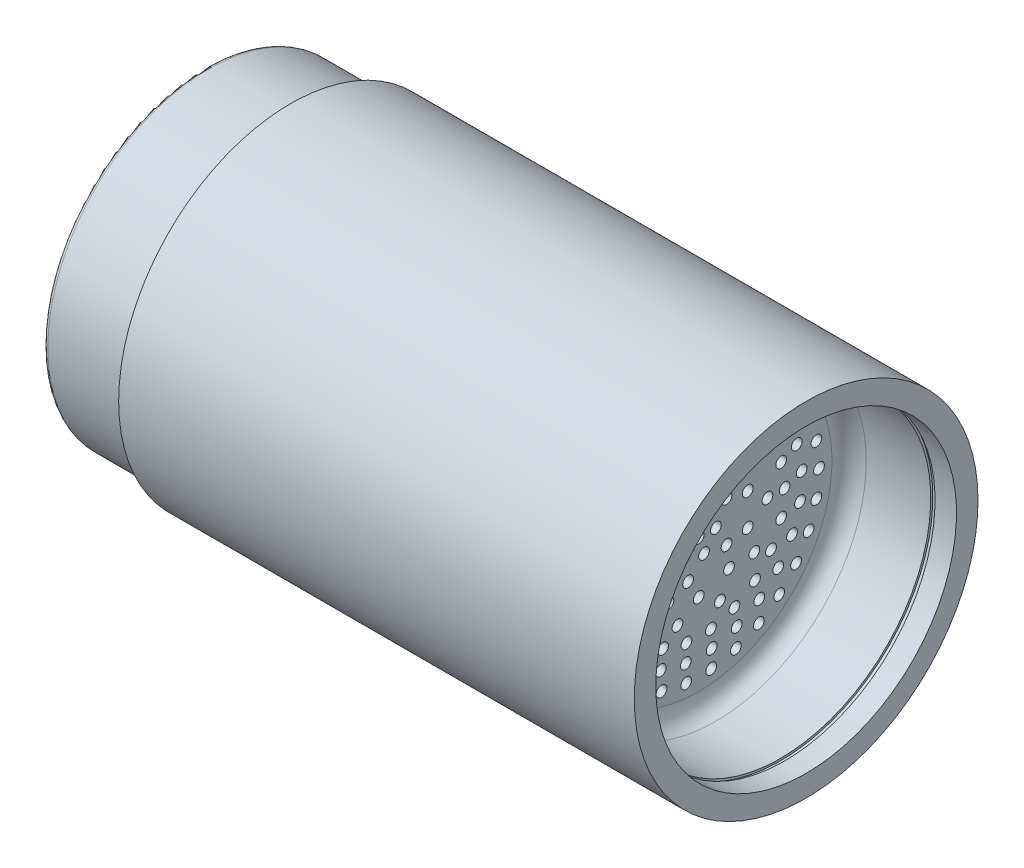
SolidWorks part; units mm, degrees
material "ABS"
ref_plane "Front Plane" through (0, 0, 0) normal (0, 0, 1) x (1, 0, 0)
ref_plane "Top Plane" through (0, 0, 0) normal (0, 1, 0) x (1, 0, 0)
ref_plane "Right Plane" through (0, 0, 0) normal (1, 0, 0) x (0, 0, -1)
sketch "Sketch1" plane through (0, 0, 0) normal (0, 0, 1) x (1, 0, 0)
  line L0 (0, 0) -> (112.0873, 0) construction
  line L1 (112.0873, 0) -> (112.0873, -50.8) construction
  line L2 (112.0873, -50.8) -> (-40.3127, -50.8)
  line L3 (-65.7127, -47.625) -> (-65.7127, -44.45)
  line L4 (-65.7127, -44.45) -> (68.9073, -44.45)
  line L5 (112.0873, -44.45) -> (112.0873, -50.8)
  line L6 (112.0873, -50.8) -> (73.9873, -50.8) construction
  line L7 (73.9873, -39.37) -> (73.9873, 0)
  line L8 (73.9873, 0) -> (80.3373, 0)
  line L9 (80.3373, 0) -> (80.3373, -39.37)
  line L10 (85.4173, -44.45) -> (104.4673, -44.45)
  line L11 (112.0873, -44.45) -> (105.7373, -44.45) construction
  line L12 (105.7373, -44.45) -> (105.7373, -45.085)
  line L13 (105.7373, -45.085) -> (104.4673, -45.085)
  line L14 (104.4673, -45.085) -> (104.4673, -44.45)
  line L15 (105.7373, -44.45) -> (112.0873, -44.45)
  line L16 (-65.7127, -50.8) -> (-40.3127, -50.8) construction
  line L17 (-40.3127, -50.8) -> (-40.3127, -47.625) construction
  line L18 (-40.3127, -47.625) -> (-65.7127, -47.625)
  line L19 (-40.3127, -47.625) -> (-40.3127, -50.8)
  arc A0 (85.4173, -44.45) -> (80.3373, -39.37) centre (85.4173, -39.37) cw
  arc A1 (73.9873, -39.37) -> (68.9073, -44.45) centre (68.9073, -39.37) cw
  point P18 (80.3373, -44.45)
  dimension "D9" = 5.08
  dimension "D1" = 50.8
  dimension "D2" = 177.8
  dimension "D3" = 6.35
  dimension "D4" = 38.1
  dimension "D5" = 6.35
  dimension "D6" = 6.35
  dimension "D7" = 1.27
  dimension "D8" = 0.635
  dimension "D10" = 25.4
revolve "Revolve1" add sketch "Sketch1" angle 360 about L0
sketch "Sketch4" plane through (80.3373, 0, 0) normal (1, 0, 0) x (0, 0, -1)
  circle A0 centre (0, 0) radius 1.5875
  circle A20 centre (5.079, 0) radius 1.5875
  circle A21 centre (1.5695, -4.8304) radius 1.5875
  circle A22 centre (-4.109, -2.9854) radius 1.5875
  circle A23 centre (-4.109, 2.9854) radius 1.5875
  circle A24 centre (0, 15.239) radius 1.5875
  circle A25 centre (8.9573, 12.3286) radius 1.5875
  circle A33 centre (14.4932, 4.7091) radius 1.5875
  circle A34 centre (14.4932, -4.7091) radius 1.5875
  circle A35 centre (8.9573, -12.3286) radius 1.5875
  circle A36 centre (0, -15.239) radius 1.5875
  circle A37 centre (-8.9573, -12.3286) radius 1.5875
  circle A40 centre (20.319, 0) radius 1.5875
  circle A41 centre (16.4384, -11.9432) radius 1.5875
  circle A42 centre (6.2789, -19.3245) radius 1.5875
  circle A43 centre (-6.2789, -19.3245) radius 1.5875
  circle A44 centre (-16.4384, -11.9432) radius 1.5875
  circle A45 centre (-20.319, 0) radius 1.5875
  circle A46 centre (-16.4384, 11.9432) radius 1.5875
  circle A47 centre (-6.2789, 19.3245) radius 1.5875
  circle A48 centre (6.2789, 19.3245) radius 1.5875
  circle A49 centre (16.4384, 11.9432) radius 1.5875
  circle A54 centre (25.399, 0) radius 1.5875
  circle A55 centre (24.3702, -7.1557) radius 1.5875
  circle A56 centre (21.367, -13.7317) radius 1.5875
  circle A57 centre (16.6328, -19.1953) radius 1.5875
  circle A58 centre (10.5511, -23.1038) radius 1.5875
  circle A59 centre (3.6147, -25.1405) radius 1.5875
  circle A60 centre (-3.6147, -25.1405) radius 1.5875
  circle A61 centre (-10.5511, -23.1038) radius 1.5875
  circle A62 centre (-16.6328, -19.1953) radius 1.5875
  circle A63 centre (-21.367, -13.7317) radius 1.5875
  circle A64 centre (-24.3702, -7.1557) radius 1.5875
  circle A65 centre (-25.399, 0) radius 1.5875
  circle A70 centre (0, 30.479) radius 1.5875
  circle A71 centre (7.5798, 29.5215) radius 1.5875
  circle A72 centre (14.6834, 26.709) radius 1.5875
  circle A73 centre (20.8643, 22.2182) radius 1.5875
  circle A74 centre (25.7343, 16.3315) radius 1.5875
  circle A75 centre (28.9873, 9.4185) radius 1.5875
  circle A76 centre (30.4189, 1.9138) radius 1.5875
  circle A77 centre (29.9392, -5.7112) radius 1.5875
  circle A78 centre (27.5782, -12.9773) radius 1.5875
  circle A79 centre (23.4845, -19.4281) radius 1.5875
  circle A80 centre (17.9151, -24.658) radius 1.5875
  circle A81 centre (11.2201, -28.3387) radius 1.5875
  circle A82 centre (3.82, -30.2387) radius 1.5875
  circle A83 centre (-3.82, -30.2387) radius 1.5875
  circle A85 centre (35.559, 0) radius 1.5875
  circle A86 centre (34.782, -7.3931) radius 1.5875
  circle A87 centre (32.4848, -14.4632) radius 1.5875
  circle A88 centre (28.7679, -20.9011) radius 1.5875
  circle A89 centre (23.7936, -26.4255) radius 1.5875
  circle A90 centre (17.7795, -30.795) radius 1.5875
  circle A91 centre (10.9883, -33.8186) radius 1.5875
  circle A92 centre (3.7169, -35.3642) radius 1.5875
  circle A93 centre (-3.7169, -35.3642) radius 1.5875
  circle A94 centre (-10.9883, -33.8186) radius 1.5875
  circle A95 centre (-17.7795, -30.795) radius 1.5875
  circle A96 centre (-23.7936, -26.4255) radius 1.5875
  circle A97 centre (-28.7679, -20.9011) radius 1.5875
  circle A98 centre (-32.4848, -14.4632) radius 1.5875
  circle A99 centre (-34.782, -7.3931) radius 1.5875
  circle A100 centre (-35.559, 0) radius 1.5875
  circle A101 centre (-34.782, 7.3931) radius 1.5875
  circle A102 centre (-32.4848, 14.4632) radius 1.5875
  circle A103 centre (-28.7679, 20.9011) radius 1.5875
  circle A104 centre (-23.7936, 26.4255) radius 1.5875
  circle A105 centre (-17.7795, 30.795) radius 1.5875
  circle A106 centre (-10.9883, 33.8186) radius 1.5875
  circle A107 centre (-11.2201, -28.3387) radius 1.5875
  circle A108 centre (-17.9151, -24.658) radius 1.5875
  circle A109 centre (-23.4845, -19.4281) radius 1.5875
  circle A110 centre (-27.5782, -12.9773) radius 1.5875
  circle A111 centre (-24.3702, 7.1557) radius 1.5875
  circle A112 centre (-21.367, 13.7317) radius 1.5875
  circle A113 centre (-16.6328, 19.1953) radius 1.5875
  circle A115 centre (1.5695, 4.8304) radius 1.5875
  circle A122 centre (-10.159, 0) radius 1.5875
  circle A123 centre (-3.1393, 9.6618) radius 1.5875
  circle A124 centre (8.2188, 5.9713) radius 1.5875
  circle A125 centre (8.2188, -5.9713) radius 1.5875
  circle A126 centre (-3.1393, -9.6618) radius 1.5875
  circle A127 centre (-14.4932, -4.7091) radius 1.5875
  circle A128 centre (-14.4932, 4.7091) radius 1.5875
  circle A129 centre (-8.9573, 12.3286) radius 1.5875
  circle A140 centre (-10.5511, 23.1038) radius 1.5875
  circle A141 centre (-3.6147, 25.1405) radius 1.5875
  circle A142 centre (3.6147, 25.1405) radius 1.5875
  circle A145 centre (-29.9392, -5.7112) radius 1.5875
  circle A146 centre (-30.4189, 1.9138) radius 1.5875
  circle A147 centre (-28.9873, 9.4185) radius 1.5875
  circle A148 centre (-25.7343, 16.3315) radius 1.5875
  circle A149 centre (-20.8643, 22.2182) radius 1.5875
  circle A150 centre (-14.6834, 26.709) radius 1.5875
  circle A151 centre (-7.5798, 29.5215) radius 1.5875
  circle A152 centre (-3.7169, 35.3642) radius 1.5875
  circle A153 centre (3.7169, 35.3642) radius 1.5875
  circle A154 centre (10.9883, 33.8186) radius 1.5875
  circle A155 centre (17.7795, 30.795) radius 1.5875
  circle A156 centre (23.7936, 26.4255) radius 1.5875
  circle A157 centre (28.7679, 20.9011) radius 1.5875
  circle A158 centre (32.4848, 14.4632) radius 1.5875
  circle A159 centre (34.782, 7.3931) radius 1.5875
  circle A160 centre (10.5511, 23.1038) radius 1.5875
  circle A161 centre (16.6328, 19.1953) radius 1.5875
  circle A162 centre (21.367, 13.7317) radius 1.5875
  circle A163 centre (24.3702, 7.1557) radius 1.5875
  point P18 (0, 0)
  point P19 (0, 0)
  point P37 (0, 0)
  point P48 (0, 0)
  point P50 (0, 0)
  point P79 (0, 0)
  point P112 (0, 0)
  point P124 (0, 0)
  point P167 (0, 0)
  point P188 (0, 0)
  dimension "D1" = 5
  dimension "D3" = 10
  dimension "D5" = 5
  dimension "D7" = 10
  dimension "D9" = 22
  dimension "D4" = 25
  dimension "D2" = 30
extrude "Cut-Extrude1" cut sketch "Sketch4" against normal through all both and the other way through all
ref_axis "Axis1" through (112.0873, 0, 0) along (-1, 0, 0)
ref_plane "Plane2" through (10.4873, 0, 0) normal (-1, 0, 0) x (0, 0, 1)
sketch "Sketch5" plane through (10.4873, 0, 0) normal (-1, 0, 0) x (0, 0, 1)
  line L0 (0, 0) -> (-59.3102, 0) construction
  line L1 (0, 0) -> (0, -50.8) construction
  arc A0 (-9.976, 43.3161) -> (9.976, 43.3161) centre (0, 44.45) ccw
  circle A1 centre (0, 0) radius 44.45 construction
  circle A2 centre (0, 0) radius 44.45 construction
  arc A4 (-12.4537, 42.6698) -> (12.4537, 42.6698) centre (0, 44.45) ccw
  arc A6 (12.4537, 42.6698) -> (9.976, 43.3161) centre (0, 0) ccw
  arc A7 (12.5527, 45.2823) -> (-12.5527, 45.2823) centre (0, 0) ccw construction
  arc A8 (-9.976, 43.3161) -> (-12.4537, 42.6698) centre (0, 0) ccw
  arc A9 (-12.5527, 45.2823) -> (12.5527, 45.2823) centre (0, 44.45) ccw construction
  arc A10 (9.976, 43.3161) -> (-9.976, 43.3161) centre (0, 0) ccw construction
  circle A11 centre (0, 0) radius 50.8 construction
  dimension "D1" = 2.54
extrude "Boss-Extrude1" add sketch "Sketch5" against normal blind 50.8
ref_plane "Plane3" through (61.2873, 0, 0) normal (1, 0, 0) x (0, 0, -1)
ref_point "Point1"
sketch "Sketch10" plane through (61.2873, 0, 0) normal (1, 0, 0) x (0, 0, -1)
  line L0 (0, 44.45) -> (-30.0251, 44.45) construction
  arc A0 (-9.976, 43.3161) -> (9.976, 43.3161) centre (0, 44.45) ccw
  arc A1 (-12.4537, 42.6698) -> (12.4537, 42.6698) centre (0, 44.45) ccw
  arc A2 (12.4537, 42.6698) -> (9.976, 43.3161) centre (0, 0) ccw
  arc A3 (-9.976, 43.3161) -> (-12.4537, 42.6698) centre (0, 0) ccw
  circle A4 centre (0, 44.45) radius 12.5803 construction
  circle A5 centre (0, 44.45) radius 10.0403 construction
  point P5 (9.6016, 47.3855)
  point P7 (12.5803, 44.45)
  dimension "D1" = 2.54
revolve "Revolve2" add sketch "Sketch10" angle 90 about L0
sketch "Sketch12" plane through (10.4873, 0, 0) normal (-1, 0, 0) x (0, 0, 1)
  line L0 (0, 0) -> (-52.6904, 0) construction
  line L1 (0, 0) -> (0, -45.085) construction
  line L2 (-7.62, 0) -> (-7.62, -10.45) construction
  line L3 (-45.72, 10.45) -> (-45.72, 11.72)
  line L4 (-7.62, -10.45) -> (-45.72, -10.45)
  line L5 (-7.62, -10.45) -> (-7.62, -11.72)
  line L6 (-7.62, -11.72) -> (-45.72, -11.72)
  line L7 (-45.72, -10.45) -> (-45.72, -11.72)
  line L8 (-7.62, 11.72) -> (-45.72, 11.72)
  line L9 (-7.62, 10.45) -> (-7.62, 11.72)
  line L10 (-7.62, 10.45) -> (-45.72, 10.45)
  line L11 (7.62, 0) -> (7.62, -10.45) construction
  line L12 (7.62, 10.45) -> (45.72, 10.45)
  line L13 (7.62, 10.45) -> (7.62, 11.72)
  line L14 (7.62, 11.72) -> (45.72, 11.72)
  line L15 (45.72, -10.45) -> (45.72, -11.72)
  line L16 (7.62, -11.72) -> (45.72, -11.72)
  line L17 (7.62, -10.45) -> (7.62, -11.72)
  line L18 (7.62, -10.45) -> (45.72, -10.45)
  line L19 (45.72, 10.45) -> (45.72, 11.72)
  circle A1 centre (0, 0) radius 45.085 construction
  dimension "D1" = 10.45
  dimension "D2" = 38.1
  dimension "D3" = 7.62
extrude "Boss-Extrude2" add sketch "Sketch12" against normal up to surface (63.5 mm away) up to face at (73.9873, 0, 26.9865)
ref_plane "Plane5" through (48.5873, 0, 0) normal (-1, 0, 0) x (0, 0, 1)
sketch "Sketch13" plane through (48.5873, 0, 0) normal (-1, 0, 0) x (0, 0, 1)
  line L0 (0, 0) -> (19, 0) construction
  line L1 (19, 0) -> (19, 10.0875)
  line L2 (19, 10.0875) -> (19, 10.45)
  line L3 (27.7805, 10.45) -> (16.9774, 10.45) construction
  line L4 (19, 10.45) -> (20.27, 10.45)
  line L5 (7.62, 10.45) -> (43.2042, 10.45) construction
  line L6 (20.27, 10.45) -> (20.27, -10.45)
  line L7 (16.9774, -10.45) -> (37.9578, -10.45) construction
  line L8 (20.27, -10.45) -> (19, -10.45)
  line L9 (43.2042, -10.45) -> (7.62, -10.45) construction
  line L10 (19, -10.45) -> (19, 0)
  line L11 (0, 0) -> (0, 18.4215) construction
  line L12 (-19, -10.45) -> (-19, 0)
  line L13 (-20.27, -10.45) -> (-19, -10.45)
  line L14 (-20.27, 10.45) -> (-20.27, -10.45)
  line L15 (-19, 10.45) -> (-20.27, 10.45)
  line L16 (-19, 10.0875) -> (-19, 10.45)
  line L17 (-19, 0) -> (-19, 10.0875)
  dimension "D1" = 19
  dimension "D2" = 1.27
extrude "Boss-Extrude3" add sketch "Sketch13" against normal up to surface (25.4 mm away) up to face at (73.9873, -0.3638, 0)
ref_plane "Plane6" through (0, -30.48, 0) normal (0, 1, 0) x (1, 0, 0)
sketch "Sketch14" plane through (0, -30.48, 0) normal (0, 1, 0) x (1, 0, 0)
  circle A7 centre (10.0346, -18.7383) radius 3.6
  circle A8 centre (10.0346, 9.2017) radius 3.6
  circle A9 centre (-42.0354, -23.8183) radius 3.6
  circle A10 centre (-40.7654, 24.4417) radius 3.6
extrude "Boss-Extrude4" add sketch "Sketch14" against normal up to surface (7.9492 mm away) up to face at (42.8223, 17.6742, -0.0306)
ref_plane "Plane7" through (10.4873, 0, 0) normal (-1, 0, 0) x (0, 0, 1)
sketch "Sketch15" plane through (10.4873, 0, 0) normal (-1, 0, 0) x (0, 0, 1)
  line L0 (0, 0) -> (0, -45.085) construction
  line L1 (0, 0) -> (-21.5156, 0) construction
  line L2 (0, 0) -> (-52.6904, 0) construction
  line L11 (45.72, -11.72) -> (45.72, -10.45)
  line L20 (-7.62, -11.72) -> (-45.72, -11.72)
  line L21 (-7.62, -11.72) -> (-7.62, -10.45)
  line L22 (-7.62, -10.45) -> (-45.72, -10.45)
  line L23 (-45.72, -11.72) -> (-45.72, -10.45)
  line L24 (7.62, -10.45) -> (45.72, -10.45)
  line L25 (7.62, -11.72) -> (45.72, -11.72)
  line L26 (7.62, -11.72) -> (7.62, -10.45)
  line L27 (7.62, 11.72) -> (7.62, 10.45)
  line L28 (7.62, 11.72) -> (45.72, 11.72)
  line L29 (7.62, 10.45) -> (45.72, 10.45)
  line L30 (-45.72, 11.72) -> (-45.72, 10.45)
  line L31 (-7.62, 10.45) -> (-45.72, 10.45)
  line L32 (-7.62, 11.72) -> (-7.62, 10.45)
  line L33 (-7.62, 11.72) -> (-45.72, 11.72)
  line L34 (45.72, 11.72) -> (45.72, 10.45)
extrude "Cut-Extrude2" cut sketch "Sketch15" against normal blind 12.7
fillet "Fillet7" radius 1.27 2 edges at (-65.7127, 0, 47.625) (-40.3127, 0, 47.625)
